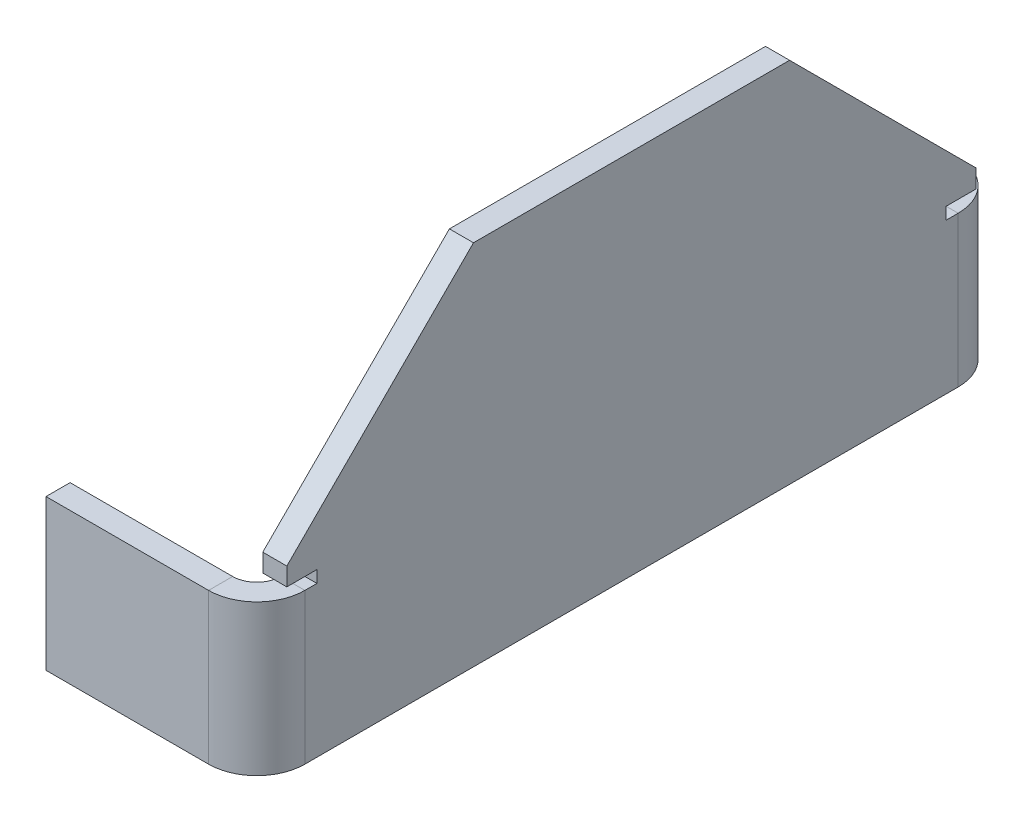
SolidWorks part; units mm, degrees
note: The reader was unsure of these and kept them because the rebuilt part matched: flange length of "边线-法兰1".
material "Q355"
ref_plane "前视基准面" through (0, 0, 0) normal (0, 0, 1) x (1, 0, 0)
ref_plane "上视基准面" through (0, 0, 0) normal (0, 1, 0) x (1, 0, 0)
ref_plane "右视基准面" through (0, 0, 0) normal (1, 0, 0) x (0, 0, -1)
sketch "草图1" plane through (0, 0, 0) normal (1, 0, 0) x (0, 0, -1)
  line L0 (-52.5, 122) -> (52.5, 122)
  line L1 (52.5, 122) -> (114.5, 60)
  line L3 (-52.5, 122) -> (-114.5, 60)
  line L5 (-124.5, 0) -> (124.5, 0)
  line L6 (0, 122) -> (0, 0) construction
  line L7 (-114.5, 60) -> (-114.5, 50)
  line L8 (-114.5, 50) -> (-124.5, 50)
  line L9 (-124.5, 50) -> (-124.5, 0)
  line L10 (114.5, 60) -> (114.5, 50)
  line L11 (114.5, 50) -> (124.5, 50)
  line L12 (124.5, 50) -> (124.5, 0)
  dimension "D1" = 122
  dimension "D2" = 105
  dimension "D3" = 135
  dimension "D4" = 50
  dimension "D5" = 10
  dimension "D6" = 10
base flange "基体-法兰1" sketch "草图1" thickness 8 reverse thickness direction no parameters "D1"=8
edge flange "边线-法兰1" sketch "草图8" flange profiles "草图8", "草图9" flange angle 90 flange length 70 flange position material inside bend radius 8 thickness 8 relief rectangular parameters "D6"=10, "D8"=1
sketch "草图8" plane through (-8, 0, 124.5) normal (0, 0, -1) x (0, -1, 0)
  line L2 (-50, 0) -> (-50, 62)
  line L3 (-50, 62) -> (0, 62)
  line L4 (0, 62) -> (0, 0)
  line L5 (0, 0) -> (-50, 0) construction
  line L6 (0, 0) -> (-50, 0)
sketch "草图9" plane through (-8, 0, -124.5) normal (0, 0, 1) x (0, 1, 0)
  line L0 (50, 0) -> (0, 0) construction
  line L1 (50, 0) -> (0, 0)
  line L2 (50, 0) -> (50, 62)
  line L3 (50, 62) -> (0, 62)
  line L4 (0, 62) -> (0, 0)
bend "边线折弯1" bend radius 8 bend angle 90 parameters "D5"=1
bend "边线折弯2" bend radius 8 bend angle 90 parameters "D5"=2
sketch "折弯-线1" [suppressed] plane through (0, 0, 0) normal (0, 1, 0) x (1, 0, 0)
sketch "边界框1" [suppressed] plane through (0, 0, 0) normal (0, 1, 0) x (1, 0, 0)
sheet metal parameters "钣金9" thickness 8 parameters "D1"=2
flat pattern "平板型式9" [suppressed]
sketch "折弯-线2" plane through (0, 0, 0) normal (0, 1, 0) x (1, 0, 0)
sketch "边界框2" [suppressed] plane through (0, 0, 0) normal (0, 1, 0) x (1, 0, 0)
sheet metal parameters "钣金10" thickness 8 parameters "D1"=2
flat pattern "平板型式9"
sketch "折弯-线2" plane through (0, 0, 0) normal (1, 0, 0) x (0, 0, -1)
  line L0 (117.9248, 0) -> (117.9248, 50) construction
  line L1 (-117.9248, 50) -> (-117.9248, 0) construction
  line L2 (117.9248, 0) -> (117.9248, 50) construction
  line L3 (-117.9248, 50) -> (-117.9248, 0) construction
sketch3d "边界框2" [suppressed]
  line L0 (-181.3496, 0, 0) -> (181.3496, 0, 0) construction
  line L1 (-181.3496, 122, 0) -> (181.3496, 122, 0) construction
  line L2 (-181.3496, 0, 0) -> (-181.3496, 122, 0) construction
  line L3 (181.3496, 0, 0) -> (181.3496, 122, 0) construction
bend of the flat pattern "展开-<边线折弯1>1"
bend of the flat pattern "展开-<边线折弯2>1"
